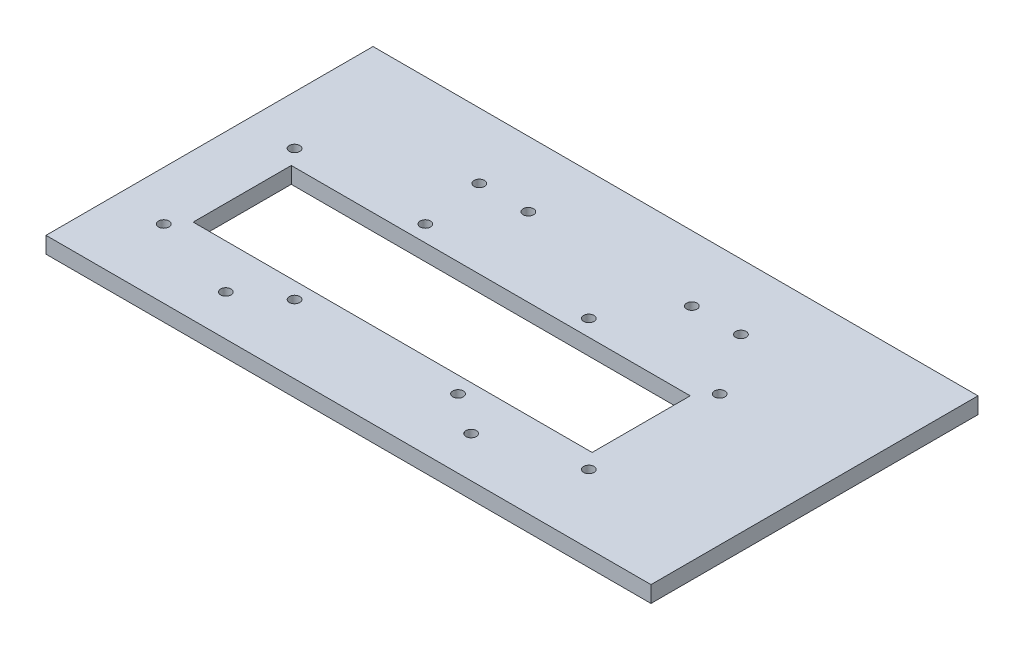
SolidWorks part; units mm, degrees
ref_plane "Front Plane" through (0, 0, 0) normal (0, 0, 1) x (1, 0, 0)
ref_plane "Top Plane" through (0, 0, 0) normal (0, 1, 0) x (1, 0, 0)
ref_plane "Right Plane" through (0, 0, 0) normal (1, 0, 0) x (0, 0, -1)
sketch "Sketch1" plane through (0, 0, 0) normal (0, 1, 0) x (1, 0, 0)
  line L0 (61, -15) -> (61, -41) construction
  line L1 (-61, -15) -> (61, -15)
  line L2 (-61, -15) -> (-61, 15)
  line L3 (-61, 15) -> (61, 15)
  line L4 (61, -15) -> (61, 15)
  line L5 (-61, -15) -> (61, 15) construction
  line L6 (-61, 15) -> (61, -15) construction
  line L11 (61, -41) -> (105, -41) construction
  line L12 (105, -41) -> (105, 59)
  line L13 (105, 59) -> (-80, 59)
  line L14 (105, -41) -> (-80, -41)
  line L15 (-80, -41) -> (-80, 59)
  point P0 (0, 0)
  point P6 (0, 0)
  dimension "D1" = 30
  dimension "D2" = 122
  dimension "D3" = 26
  dimension "D4" = 44
  dimension "D5" = 100
  dimension "D6" = 185
extrude "Boss-Extrude1" add sketch "Sketch1" along normal blind 5
sketch "Sketch2" plane through (0, 0, 0) normal (0, 1, 0) x (1, 0, 0)
  line L1 (25, -20) -> (-25, -20) construction
  line L2 (25, -20) -> (25, 20) construction
  line L3 (25, 20) -> (-25, 20) construction
  line L4 (-25, -20) -> (-25, 20) construction
  line L5 (25, -20) -> (-25, 20) construction
  line L6 (25, 20) -> (-25, -20) construction
  line L7 (65, -20) -> (-65, -20) construction
  line L8 (65, -20) -> (65, 20) construction
  line L9 (65, 20) -> (-65, 20) construction
  line L10 (-65, -20) -> (-65, 20) construction
  line L11 (65, -20) -> (-65, 20) construction
  line L12 (65, 20) -> (-65, -20) construction
  circle A0 centre (-25, 20) radius 1.6
  circle A1 centre (25, 20) radius 1.6
  circle A2 centre (25, -20) radius 1.6
  circle A3 centre (-25, -20) radius 1.6
  circle A4 centre (-65, 20) radius 1.6
  circle A5 centre (65, 20) radius 1.6
  circle A6 centre (65, -20) radius 1.6
  circle A7 centre (-65, -20) radius 1.6
  point P0 (0, 0)
  point P7 (0, 0)
  dimension "D3" = 3.2
  dimension "D8" = 3.2
  dimension "D1" = 50
  dimension "D2" = 40
  dimension "D6" = 130
  dimension "D7" = 40
  dimension "D4" = 2
  dimension "D5" = 2
  dimension "D9" = 2
  dimension "D10" = 2
extrude "Cut-Extrude2" cut sketch "Sketch2" along normal up to next
sketch "Sketch3" plane through (0, 5, 0) normal (0, 1, 0) x (1, 0, 0)
  line L0 (12.5, 59) -> (12.5, 39) construction
  line L1 (105, 59) -> (-80, 59) construction
  line L2 (12.5, 39) -> (-12.5, 39) construction
  line L3 (-12.5, 39) -> (-27.5, 39) construction
  circle A0 centre (-27.5, 39) radius 1.6
  circle A1 centre (-12.5, 39) radius 1.6
  circle A2 centre (37.5, 39) radius 1.6
  circle A3 centre (52.5, 39) radius 1.6
  dimension "D3" = 3.2
  dimension "D4" = 3.2
  dimension "D1" = 20
  dimension "D2" = 25
  dimension "D5" = 15
extrude "Cut-Extrude3" cut sketch "Sketch3" against normal up to next
sketch "Sketch4" plane through (0, 5, 0) normal (0, 1, 0) x (1, 0, 0)
  line L0 (0, -15) -> (0, -28.5) construction
  line L1 (-61, -15) -> (61, -15) construction
  line L2 (0, -28.5) -> (-37.5, -28.5) construction
  circle A0 centre (-37.5, -28.5) radius 1.6
  circle A1 centre (37.5, -28.5) radius 1.6
  dimension "D3" = 3.2
  dimension "D1" = 13.5
  dimension "D2" = 37.5
extrude "Cut-Extrude4" cut sketch "Sketch4" against normal up to next
